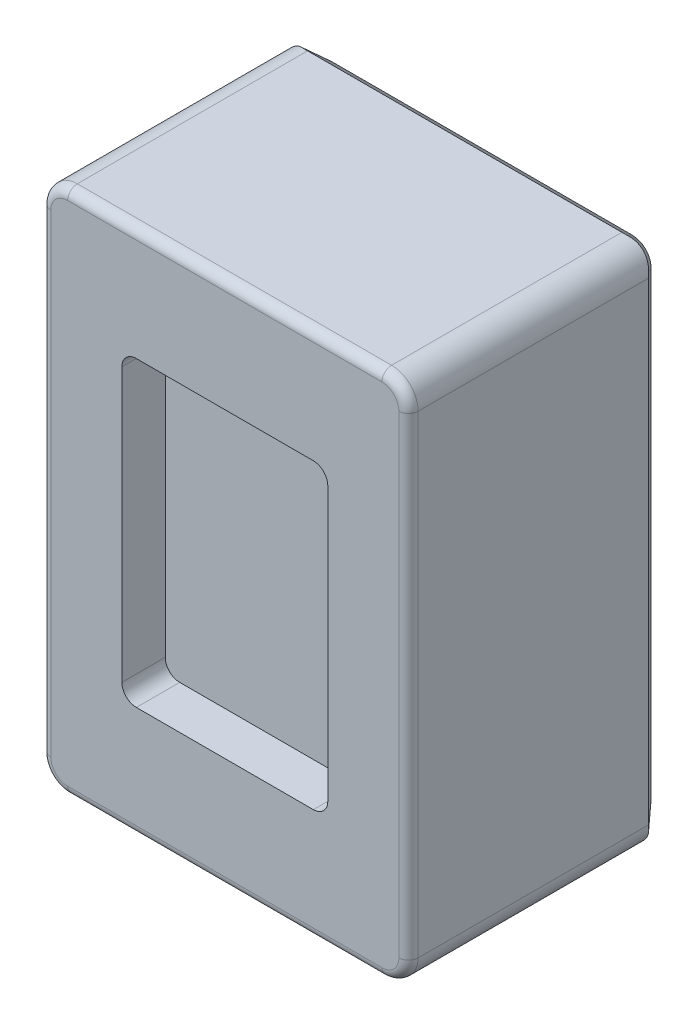
SolidWorks part; units mm, degrees
ref_plane "Front Plane" through (0, 0, 0) normal (0, 0, 1) x (1, 0, 0)
ref_plane "Top Plane" through (0, 0, 0) normal (0, 1, 0) x (1, 0, 0)
ref_plane "Right Plane" through (0, 0, 0) normal (1, 0, 0) x (0, 0, -1)
sketch "Sketch2" plane through (0, 0, 0) normal (0, 0, 1) x (1, 0, 0)
  line L1 (0, 0) -> (76.2, 0)
  line L2 (0, 0) -> (0, 109.22)
  line L3 (0, 109.22) -> (76.2, 109.22)
  line L4 (76.2, 0) -> (76.2, 109.22)
  dimension "D1" = 109.22
  dimension "D2" = 76.2
extrude "Boss-Extrude1" add sketch "Sketch2" along normal blind 53.34
chamfer "Chamfer1" distance 3 angle 50 1 edges at (38.1, 109.22, 0) first distance on face at (38.1, 54.61, 0)
chamfer "Chamfer2" distance 3 angle 50 3 edges at (0, 53.11, 0) (38.1, 0, 0) (76.2, 53.11, 0) first distance on face at (38.1, 53.11, 0)
fillet "Fillet2" radius 5.5 4 edges at (1.5, 1.5, 1.7876) (74.7, 1.5, 1.7876) (74.7, 107.72, 1.7876) (1.5, 107.72, 1.7876)
fillet "Fillet3" radius 5.5 4 edges at (76.2, 0, 29.1396) (0, 0, 29.1396) (0, 109.22, 29.1396) (76.2, 109.22, 29.1396)
fillet "Fillet4" radius 2 8 edges at (1.6109, 1.6109, 53.34) (0, 54.61, 53.34) (1.6109, 107.6091, 53.34) (38.1, 109.22, 53.34) (74.5891, 107.6091, 53.34) (76.2, 54.61, 53.34) (74.5891, 1.6109, 53.34) (38.1, 0, 53.34)
sketch "Sketch4" plane through (0, 0, 53.34) normal (0, 0, 1) x (1, 0, 0)
  line L0 (38.1, 109.22) -> (38.1, 0) construction
  line L1 (19.7416, 85.9478) -> (56.4584, 85.9478)
  line L2 (16.7416, 82.9478) -> (16.7416, 26.2722)
  line L3 (19.7416, 23.2722) -> (56.4584, 23.2722)
  line L4 (59.4584, 82.9478) -> (59.4584, 26.2722)
  line L5 (5.5, 109.22) -> (70.7, 109.22) construction
  line L6 (70.7, 0) -> (5.5, 0) construction
  line L7 (0, 54.61) -> (76.2, 54.61) construction
  line L8 (0, 5.5) -> (0, 103.72) construction
  line L9 (76.2, 103.72) -> (76.2, 5.5) construction
  arc A0 (16.7416, 26.2722) -> (19.7416, 23.2722) centre (19.7416, 26.2722) ccw
  arc A1 (56.4584, 23.2722) -> (59.4584, 26.2722) centre (56.4584, 26.2722) ccw
  arc A2 (19.7416, 85.9478) -> (16.7416, 82.9478) centre (19.7416, 82.9478) ccw
  arc A3 (56.4584, 85.9478) -> (59.4584, 82.9478) centre (56.4584, 82.9478) cw
  point P16 (38.1, 85.9478)
  point P17 (38.1, 54.61)
  point P18 (16.7416, 54.61)
  dimension "D1" = 3
extrude "Cut-Extrude1" cut sketch "Sketch4" against normal blind 9
sketch "Sketch5" plane through (0, 0, 0) normal (0, -1, 0) x (1, 0, 0)
  line L0 (0, 51.34) -> (76.2, 51.34) construction
  line L1 (14.6, 36.34) -> (61.6, 36.34)
  line L2 (13.1, 37.84) -> (13.1, 44.84)
  line L3 (14.6, 46.34) -> (61.6, 46.34)
  line L4 (63.1, 37.84) -> (63.1, 44.84)
  line L5 (5.5, 53.34) -> (70.7, 53.34) construction
  arc A0 (2, 53.34) -> (0, 51.34) centre (2, 51.34) ccw construction
  arc A1 (61.6, 36.34) -> (63.1, 37.84) centre (61.6, 37.84) ccw
  arc A2 (14.6, 36.34) -> (13.1, 37.84) centre (14.6, 37.84) cw
  arc A3 (13.1, 44.84) -> (14.6, 46.34) centre (14.6, 44.84) cw
  arc A4 (61.6, 46.34) -> (63.1, 44.84) centre (61.6, 44.84) cw
  point P10 (38.1, 46.34)
  point P11 (38.1, 51.34)
  point P16 (63.1, 36.34)
  point P19 (13.1, 36.34)
  point P24 (63.1, 46.34)
  dimension "D4" = 1.5
  dimension "D1" = 10
  dimension "D2" = 7
  dimension "D3" = 50
extrude "Cut-Extrude2" cut sketch "Sketch5" against normal blind 3
